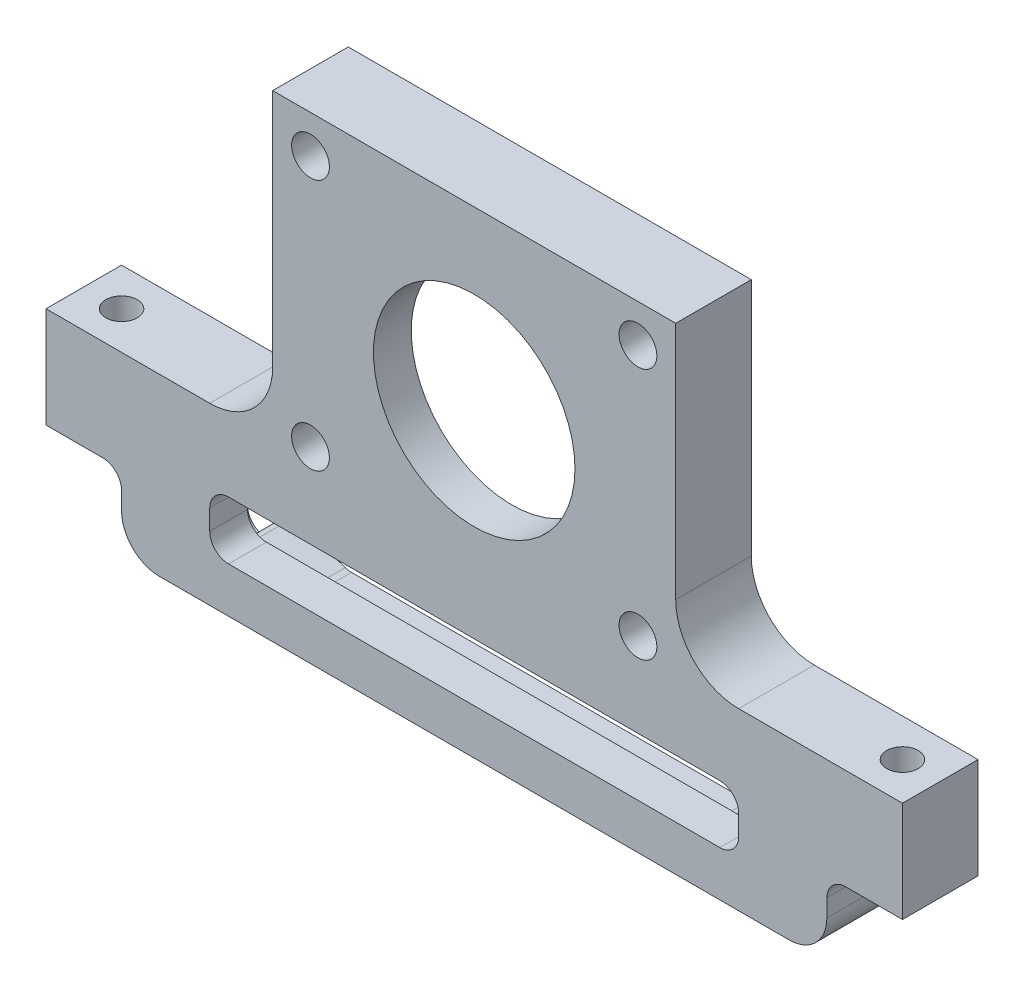
SolidWorks part; units mm, degrees
material "1060 Alloy"
ref_plane "Front Plane" through (0, 0, 0) normal (0, 0, 1) x (1, 0, 0)
ref_plane "Top Plane" through (0, 0, 0) normal (0, 1, 0) x (1, 0, 0)
ref_plane "Right Plane" through (0, 0, 0) normal (1, 0, 0) x (0, 0, -1)
sketch "Sketch1" plane through (0, 0, 0) normal (0, 0, 1) x (1, 0, 0)
  line L0 (18, 32) -> (50, 32)
  line L1 (6, 0) -> (6, -5.9)
  line L2 (50, 32) -> (50, 8)
  line L3 (18, 32) -> (18, 8)
  line L4 (13, 2.3) -> (55, 2.3)
  line L5 (13, 2.3) -> (13, -2.3)
  line L6 (13, -2.3) -> (55, -2.3)
  line L7 (55, 2.3) -> (55, -2.3)
  line L8 (6, -5.9) -> (62, -5.9)
  line L9 (62, -5.9) -> (62, 0)
  line L10 (6, 0) -> (0, 0)
  line L11 (0, 0) -> (0, 8)
  line L12 (0, 8) -> (18, 8)
  line L13 (50, 8) -> (68, 8)
  line L14 (68, 8) -> (68, 0)
  line L15 (68, 0) -> (62, 0)
  circle A0 centre (34, 18) radius 8
  dimension "D4" = 16
  dimension "D1" = 4.6
  dimension "D2" = 42
  dimension "D3" = 3.6
  dimension "D5" = 7
  dimension "D7" = 32
  dimension "D8" = 16
  dimension "D9" = 18
  dimension "D10" = 8
  dimension "D11" = 15.7
  dimension "D13" = 68
  dimension "D14" = 32
  dimension "D15" = 56
extrude "Boss-Extrude1" add sketch "Sketch1" along normal blind 6
sketch "Sketch3" plane through (0, 0, 0) normal (0, 0, -1) x (-1, 0, 0)
  circle A0 centre (-34, 18) radius 13
  dimension "D1" = 26
extrude "Cut-Extrude2" cut sketch "Sketch3" against normal offset from surface (3 mm away) 3 up to face at (34, 0, 6)
hole_wizard "Tap Drill for M3 Tap2" positions "Sketch5" profile "Sketch4" hole size "M3" standard "ISO"
sketch "Sketch5" plane through (38.1016, 0, -22.7468) normal (0, -1, 0) x (-1, 0, 0)
  line L3 (-29.8984, -28.7468) -> (-29.8984, -22.7468) construction
  line L4 (38.1016, -28.7468) -> (38.1016, -22.7468) construction
  line L5 (-23.8984, -28.7468) -> (-29.8984, -28.7468) construction
  point P0 (35.1016, -25.7468)
  point P2 (-26.8984, -25.7468)
  dimension "D1" = 3
  dimension "D2" = 3
  dimension "D3" = 3
sketch "Sketch4" plane through (3, 0, 3) normal (1, 0, 0) x (0, 0, -1)
  line L0 (0, 0) -> (0, 8.7511)
  line L1 (0, 8.7511) -> (1.25, 8)
  line L2 (1.25, 8) -> (1.25, 0)
  line L5 (1.25, 0) -> (0, 0)
  line L10 (0, 8.7511) -> (-1.25, 8) construction
  line L11 (0, -6.35) -> (0, 107.95) construction
  dimension "Hole Dia." = 2.5
  dimension "Hole Depth" = 8
  dimension "Drill Angle" = 118
sketch "Sketch10" plane through (0, 0, 0) normal (0, 0, -1) x (-1, 0, 0)
  line L1 (-58, 4) -> (-10, 4)
  line L2 (-58, 4) -> (-58, -4)
  line L3 (-58, -4) -> (-10, -4)
  line L4 (-10, 4) -> (-10, -4)
  line L7 (-55, -2.3) -> (-55, 2.3) construction
  line L8 (-55, 2.3) -> (-13, 2.3) construction
  line L10 (-13, 2.3) -> (-13, -2.3) construction
  dimension "D1" = 8
  dimension "D2" = 1.7
  dimension "D3" = 3
  dimension "D4" = 3
extrude "Cut-Extrude5" cut sketch "Sketch10" against normal blind 3
fillet "Fillet6" radius 1.5 4 edges at (55, 2.3, 4.5) (55, -2.3, 4.5) (13, -2.3, 4.5) (13, 2.3, 4.5)
fillet "Fillet1" radius 2 4 edges at (10, -4, 1.5) (10, 4, 1.5) (58, -4, 1.5) (58, 4, 1.5)
sketch "Sketch14" plane through (0, 0, 6) normal (0, 0, 1) x (1, 0, 0)
  line L0 (50, 32) -> (18, 32) construction
  line L1 (18, 32) -> (50, 32) construction
  line L2 (18, 32) -> (18, 6) construction
  line L3 (18, 6) -> (50, 6) construction
  line L4 (50, 32) -> (50, 6) construction
  line L5 (50, 8) -> (50, 32) construction
  line L6 (18, 32) -> (18, 8) construction
  circle A0 centre (21, 29) radius 1.5
  circle A1 centre (47, 29) radius 1.5
  circle A2 centre (21, 9) radius 1.5
  circle A3 centre (47, 9) radius 1.5
  dimension "D1" = 3
  dimension "D2" = 3
  dimension "D3" = 3
  dimension "D4" = 3
  dimension "D5" = 3
  dimension "D6" = 26
extrude "Cut-Extrude7" cut sketch "Sketch14" against normal through all
fillet "Fillet4" radius 1.5 2 edges at (6, 0, 3) (62, 0, 3)
fillet "Fillet7" radius 5 2 edges at (18, 8, 3) (50, 8, 3)
fillet "Fillet8" radius 3 2 edges at (6, -5.9, 3) (62, -5.9, 3)
sketch "Sketch15" plane through (0, 0, 0) normal (0, 0, -1) x (-1, 0, 0)
  line L0 (-58, 2) -> (-58, -2) construction
  line L1 (-58, 5) -> (-55, 5)
  line L2 (-58, 5) -> (-58, -5)
  line L3 (-58, -5) -> (-55, -5)
  line L4 (-55, 5) -> (-55, -5)
  line L5 (-56, -4) -> (-12, -4) construction
  line L6 (-12, 4) -> (-56, 4) construction
  dimension "D1" = 3
  dimension "D2" = 1
  dimension "D3" = 1
extrude "Cut-Extrude8" cut sketch "Sketch15" against normal up to surface (3 mm away) up to face at (34, 0, 3)
sketch "Sketch16" plane through (0, 0, 0) normal (0, 0, -1) x (-1, 0, 0)
  line L0 (-54.3392, 2.5266) -> (-50, 4)
  line L1 (-12, 4) -> (-55, 4) construction
  line L2 (-50, 4) -> (-55, 4)
  line L3 (-55, 4) -> (-55, 3)
  line L4 (-54.3392, -2.5266) -> (-50, -4)
  line L5 (-55, -4) -> (-12, -4) construction
  line L6 (-50, -4) -> (-55, -4)
  line L7 (-55, -4) -> (-55, -3)
  arc A0 (-55, 3) -> (-54.3392, 2.5266) centre (-54.5, 3) ccw
  arc A1 (-55, -3) -> (-54.3392, -2.5266) centre (-54.5, -3) cw
  dimension "D2" = 0.5
  dimension "D1" = 5
  dimension "D3" = 1
  dimension "D4" = 1
extrude "Boss-Extrude2" add sketch "Sketch16" against normal up to surface (3 mm away) up to face at (37.9172, 0, 3)
fillet "Fillet9" radius 1.5 6 edges at (50, -4, 1.5) (50, 4, 1.5) (55, -5, 1.5) (58, -5, 1.5) (55, 5, 1.5) (58, 5, 1.5)
ref_plane "Plane1" through (34, 0, 0) normal (-1, 0, 0) x (0, 0, 1)
mirror "Mirror1" about plane through (34, 0, 0) normal (-1, 0, 0) of "Cut-Extrude8", "Boss-Extrude2", "Fillet9"
